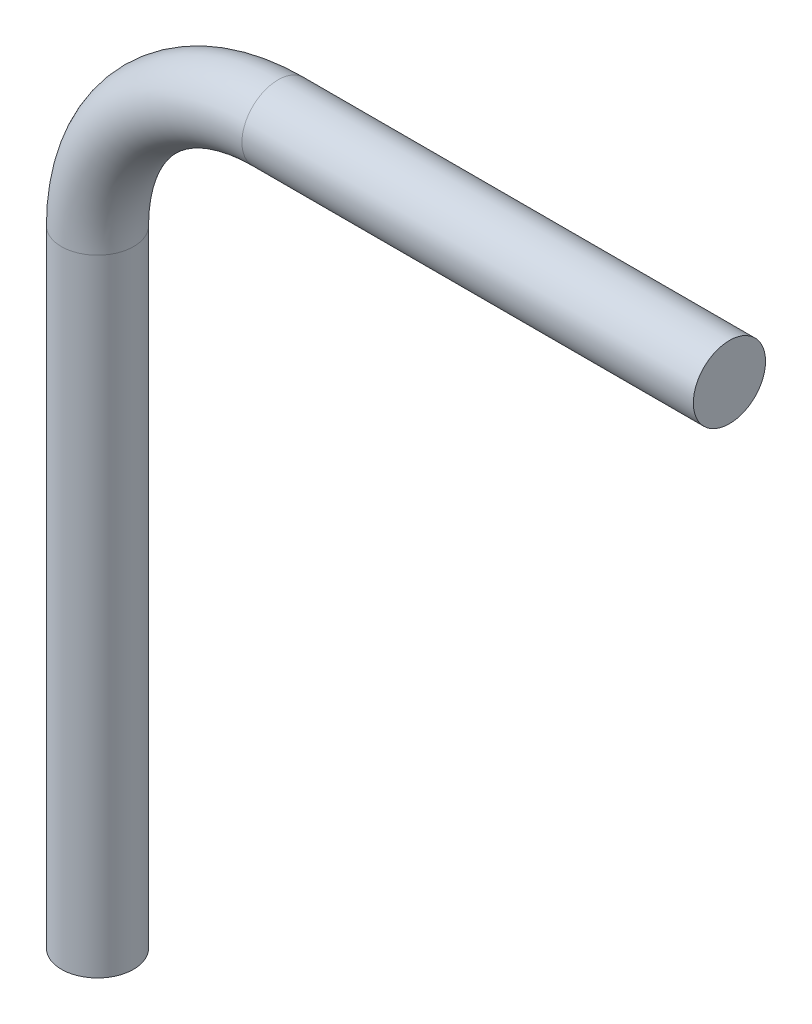
SolidWorks part; units mm, degrees
material "Copper"
ref_plane "Front Plane" through (0, 0, 0) normal (0, 0, 1) x (1, 0, 0)
ref_plane "Top Plane" through (0, 0, 0) normal (0, 1, 0) x (1, 0, 0)
ref_plane "Right Plane" through (0, 0, 0) normal (1, 0, 0) x (0, 0, -1)
sketch "Sketch1" plane through (0, 0, 0) normal (1, 0, 0) x (0, 0, -1)
  circle A0 centre (0, 0) radius 0.4
  dimension "D1" = 0.8
extrude "Boss-Extrude1" add sketch "Sketch1" along normal mid plane 5
sketch "Sketch2" plane through (0, 0, 0) normal (0, 0, 1) x (1, 0, 0)
  line L0 (-2.5, 0.4) -> (-2.5, -0.4) construction
  line L1 (-4.5, -2) -> (-4.5, -8.9334)
  arc A0 (-2.5, 0) -> (-4.5, -2) centre (-2.5, -2) ccw
  dimension "D1" = 2
  dimension "D2" = 6.9334
sweep "Sweep1" add path "Sketch2" circular profile diameter 0.8 parameters "D3"=0.8
